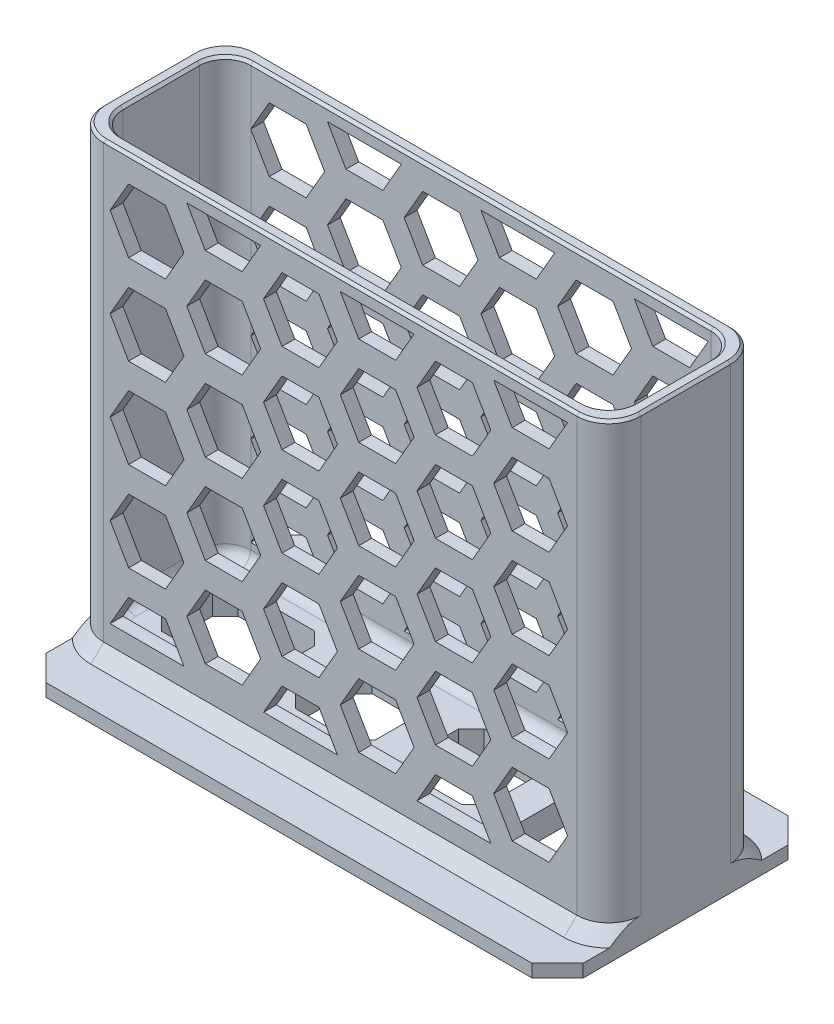
SolidWorks part; units mm, degrees
ref_plane "Front Plane" through (0, 0, 0) normal (0, 0, 1) x (1, 0, 0)
ref_plane "Top Plane" through (0, 0, 0) normal (0, 1, 0) x (1, 0, 0)
ref_plane "Right Plane" through (0, 0, 0) normal (1, 0, 0) x (0, 0, -1)
sketch "Sketch1" plane through (0, 0, 0) normal (0, 1, 0) x (1, 0, 0)
  line L1 (-105, 30) -> (105, 30)
  line L2 (-105, 30) -> (-105, -30)
  line L3 (-105, -30) -> (105, -30)
  line L4 (105, 30) -> (105, -30)
  point P0 (0, 0)
  point P6 (0, 0)
  dimension "D1" = 210
  dimension "D2" = 60
extrude "Boss-Extrude1" add sketch "Sketch1" along normal blind 5
sketch "Sketch2" plane through (0, 5, 0) normal (0, 1, 0) x (1, 0, 0)
  line L1 (-100, 25) -> (100, 25)
  line L2 (-100, 25) -> (-100, -25)
  line L3 (-100, -25) -> (100, -25)
  line L4 (100, 25) -> (100, -25)
  line L5 (-100, 25) -> (100, -25) construction
  line L6 (-100, -25) -> (100, 25) construction
  line L7 (-105, -30) -> (105, -30)
  line L8 (-105, -30) -> (-105, 30)
  line L9 (-105, 30) -> (105, 30)
  line L10 (105, -30) -> (105, 30)
  line L11 (-105, -30) -> (105, 30) construction
  line L12 (-105, 30) -> (105, -30) construction
  point P0 (0, 0)
  point P6 (0, 0)
  dimension "D1" = 200
  dimension "D2" = 50
extrude "Boss-Extrude2" add sketch "Sketch2" along normal blind 170
fillet "Fillet1" radius 10 4 edges at (100, 90, 25) (-100, 90, 25) (100, 90, -25) (-100, 90, -25)
fillet "Fillet2" radius 12.5 4 edges at (105, 87.5, 30) (105, 87.5, -30) (-105, 87.5, 30) (-105, 87.5, -30)
fillet "Fillet3" radius 5 8 edges at (97.0711, 5, -22.0711) (100, 5, 0) (97.0711, 5, 22.0711) (0, 5, 25) (-97.0711, 5, 22.0711) (-100, 5, 0) (-97.0711, 5, -22.0711) (0, 5, -25)
sketch "Sketch3" plane through (0, 0, 30) normal (0, 0, 1) x (1, 0, 0)
  line L0 (-61.1325, 117.5) -> (-68.3494, 130)
  line L1 (-61.1325, 152.5) -> (-68.3494, 165)
  line L2 (-68.3494, 165) -> (-82.7831, 165)
  line L3 (-82.7831, 165) -> (-90, 152.5)
  line L4 (-90, 152.5) -> (-82.7831, 140)
  line L5 (-82.7831, 140) -> (-68.3494, 140)
  line L6 (-68.3494, 140) -> (-61.1325, 152.5)
  line L7 (-68.3494, 130) -> (-82.7831, 130)
  line L8 (-82.7831, 130) -> (-90, 117.5)
  line L9 (-90, 117.5) -> (-82.7831, 105)
  line L10 (-82.7831, 105) -> (-68.3494, 105)
  line L11 (-68.3494, 105) -> (-61.1325, 117.5)
  line L12 (-61.1325, 82.5) -> (-68.3494, 95)
  line L13 (-68.3494, 95) -> (-82.7831, 95)
  line L14 (-82.7831, 95) -> (-90, 82.5)
  line L15 (-90, 82.5) -> (-82.7831, 70)
  line L16 (-82.7831, 70) -> (-68.3494, 70)
  line L17 (-68.3494, 70) -> (-61.1325, 82.5)
  line L18 (-61.1325, 47.5) -> (-68.3494, 60)
  line L19 (-68.3494, 60) -> (-82.7831, 60)
  line L20 (-82.7831, 60) -> (-90, 47.5)
  line L21 (-90, 47.5) -> (-82.7831, 35)
  line L22 (-82.7831, 35) -> (-68.3494, 35)
  line L23 (-68.3494, 35) -> (-61.1325, 47.5)
  line L24 (-61.1325, 12.5) -> (-68.3494, 25)
  line L25 (-68.3494, 25) -> (-82.7831, 25)
  line L26 (-82.7831, 25) -> (-90, 12.5)
  line L31 (0, 170) -> (28.8675, 170)
  line L32 (60, 170) -> (88.8675, 170)
  line L33 (-38.3494, 157.5) -> (-31.1325, 170)
  line L34 (-52.7831, 147.5) -> (-60, 135)
  line L35 (-31.1325, 100) -> (-38.3494, 112.5)
  line L36 (-38.3494, 77.5) -> (-52.7831, 77.5)
  line L37 (-38.3494, 17.5) -> (-31.1325, 30)
  line L39 (-52.7831, 52.5) -> (-38.3494, 52.5)
  line L40 (-38.3494, 147.5) -> (-52.7831, 147.5)
  line L41 (-38.3494, 52.5) -> (-31.1325, 65)
  line L42 (-31.1325, 135) -> (-38.3494, 147.5)
  line L43 (-52.7831, 157.5) -> (-38.3494, 157.5)
  line L44 (-60, 170) -> (-52.7831, 157.5)
  line L45 (-60, 135) -> (-52.7831, 122.5)
  line L46 (-31.1325, 65) -> (-38.3494, 77.5)
  line L47 (-38.3494, 122.5) -> (-31.1325, 135)
  line L48 (-52.7831, 17.5) -> (-38.3494, 17.5)
  line L49 (-52.7831, 87.5) -> (-38.3494, 87.5)
  line L50 (-38.3494, 87.5) -> (-31.1325, 100)
  line L51 (-52.7831, 42.5) -> (-60, 30)
  line L52 (-60, 100) -> (-52.7831, 87.5)
  line L53 (-31.1325, 30) -> (-38.3494, 42.5)
  line L54 (-52.7831, 77.5) -> (-60, 65)
  line L55 (-60, 65) -> (-52.7831, 52.5)
  line L57 (-38.3494, 112.5) -> (-52.7831, 112.5)
  line L58 (-52.7831, 112.5) -> (-60, 100)
  line L59 (-38.3494, 42.5) -> (-52.7831, 42.5)
  line L60 (-52.7831, 122.5) -> (-38.3494, 122.5)
  line L61 (-60, 30) -> (-52.7831, 17.5)
  line L62 (-1.1325, 117.5) -> (-8.3494, 130)
  line L63 (-1.1325, 152.5) -> (-8.3494, 165)
  line L64 (-8.3494, 165) -> (-22.7831, 165)
  line L65 (-22.7831, 165) -> (-30, 152.5)
  line L66 (-30, 152.5) -> (-22.7831, 140)
  line L67 (-22.7831, 140) -> (-8.3494, 140)
  line L68 (-8.3494, 140) -> (-1.1325, 152.5)
  line L69 (-8.3494, 130) -> (-22.7831, 130)
  line L70 (-22.7831, 130) -> (-30, 117.5)
  line L71 (-30, 117.5) -> (-22.7831, 105)
  line L72 (-22.7831, 105) -> (-8.3494, 105)
  line L73 (-8.3494, 105) -> (-1.1325, 117.5)
  line L74 (-1.1325, 82.5) -> (-8.3494, 95)
  line L75 (-8.3494, 95) -> (-22.7831, 95)
  line L76 (-22.7831, 95) -> (-30, 82.5)
  line L77 (-30, 82.5) -> (-22.7831, 70)
  line L78 (-22.7831, 70) -> (-8.3494, 70)
  line L79 (-8.3494, 70) -> (-1.1325, 82.5)
  line L80 (-1.1325, 47.5) -> (-8.3494, 60)
  line L81 (-8.3494, 60) -> (-22.7831, 60)
  line L82 (-22.7831, 60) -> (-30, 47.5)
  line L83 (-30, 47.5) -> (-22.7831, 35)
  line L84 (-22.7831, 35) -> (-8.3494, 35)
  line L85 (-8.3494, 35) -> (-1.1325, 47.5)
  line L86 (-1.1325, 12.5) -> (-8.3494, 25)
  line L87 (-8.3494, 25) -> (-22.7831, 25)
  line L88 (-22.7831, 25) -> (-30, 12.5)
  line L93 (21.6506, 157.5) -> (28.8675, 170)
  line L94 (7.2169, 147.5) -> (0, 135)
  line L95 (28.8675, 100) -> (21.6506, 112.5)
  line L96 (21.6506, 77.5) -> (7.2169, 77.5)
  line L97 (21.6506, 17.5) -> (28.8675, 30)
  line L99 (7.2169, 52.5) -> (21.6506, 52.5)
  line L100 (21.6506, 147.5) -> (7.2169, 147.5)
  line L101 (21.6506, 52.5) -> (28.8675, 65)
  line L102 (28.8675, 135) -> (21.6506, 147.5)
  line L103 (7.2169, 157.5) -> (21.6506, 157.5)
  line L104 (0, 170) -> (7.2169, 157.5)
  line L105 (0, 135) -> (7.2169, 122.5)
  line L106 (28.8675, 65) -> (21.6506, 77.5)
  line L107 (21.6506, 122.5) -> (28.8675, 135)
  line L108 (7.2169, 17.5) -> (21.6506, 17.5)
  line L109 (7.2169, 87.5) -> (21.6506, 87.5)
  line L110 (21.6506, 87.5) -> (28.8675, 100)
  line L111 (7.2169, 42.5) -> (0, 30)
  line L112 (0, 100) -> (7.2169, 87.5)
  line L113 (28.8675, 30) -> (21.6506, 42.5)
  line L114 (7.2169, 77.5) -> (0, 65)
  line L115 (0, 65) -> (7.2169, 52.5)
  line L117 (21.6506, 112.5) -> (7.2169, 112.5)
  line L118 (7.2169, 112.5) -> (0, 100)
  line L119 (21.6506, 42.5) -> (7.2169, 42.5)
  line L120 (7.2169, 122.5) -> (21.6506, 122.5)
  line L121 (0, 30) -> (7.2169, 17.5)
  line L122 (58.8675, 117.5) -> (51.6506, 130)
  line L123 (58.8675, 152.5) -> (51.6506, 165)
  line L124 (51.6506, 165) -> (37.2169, 165)
  line L125 (37.2169, 165) -> (30, 152.5)
  line L126 (30, 152.5) -> (37.2169, 140)
  line L127 (37.2169, 140) -> (51.6506, 140)
  line L128 (51.6506, 140) -> (58.8675, 152.5)
  line L129 (51.6506, 130) -> (37.2169, 130)
  line L130 (37.2169, 130) -> (30, 117.5)
  line L131 (30, 117.5) -> (37.2169, 105)
  line L132 (37.2169, 105) -> (51.6506, 105)
  line L133 (51.6506, 105) -> (58.8675, 117.5)
  line L134 (58.8675, 82.5) -> (51.6506, 95)
  line L135 (51.6506, 95) -> (37.2169, 95)
  line L136 (37.2169, 95) -> (30, 82.5)
  line L137 (30, 82.5) -> (37.2169, 70)
  line L138 (37.2169, 70) -> (51.6506, 70)
  line L139 (51.6506, 70) -> (58.8675, 82.5)
  line L140 (58.8675, 47.5) -> (51.6506, 60)
  line L141 (51.6506, 60) -> (37.2169, 60)
  line L142 (37.2169, 60) -> (30, 47.5)
  line L143 (30, 47.5) -> (37.2169, 35)
  line L144 (37.2169, 35) -> (51.6506, 35)
  line L145 (51.6506, 35) -> (58.8675, 47.5)
  line L146 (58.8675, 12.5) -> (51.6506, 25)
  line L147 (51.6506, 25) -> (37.2169, 25)
  line L148 (37.2169, 25) -> (30, 12.5)
  line L153 (81.6506, 157.5) -> (88.8675, 170)
  line L154 (67.2169, 147.5) -> (60, 135)
  line L155 (88.8675, 100) -> (81.6506, 112.5)
  line L156 (81.6506, 77.5) -> (67.2169, 77.5)
  line L157 (81.6506, 17.5) -> (88.8675, 30)
  line L159 (67.2169, 52.5) -> (81.6506, 52.5)
  line L160 (81.6506, 147.5) -> (67.2169, 147.5)
  line L161 (81.6506, 52.5) -> (88.8675, 65)
  line L162 (88.8675, 135) -> (81.6506, 147.5)
  line L163 (67.2169, 157.5) -> (81.6506, 157.5)
  line L164 (60, 170) -> (67.2169, 157.5)
  line L165 (60, 135) -> (67.2169, 122.5)
  line L166 (88.8675, 65) -> (81.6506, 77.5)
  line L167 (81.6506, 122.5) -> (88.8675, 135)
  line L168 (67.2169, 17.5) -> (81.6506, 17.5)
  line L169 (67.2169, 87.5) -> (81.6506, 87.5)
  line L170 (81.6506, 87.5) -> (88.8675, 100)
  line L171 (67.2169, 42.5) -> (60, 30)
  line L172 (60, 100) -> (67.2169, 87.5)
  line L173 (88.8675, 30) -> (81.6506, 42.5)
  line L174 (67.2169, 77.5) -> (60, 65)
  line L175 (60, 65) -> (67.2169, 52.5)
  line L177 (81.6506, 112.5) -> (67.2169, 112.5)
  line L178 (67.2169, 112.5) -> (60, 100)
  line L179 (81.6506, 42.5) -> (67.2169, 42.5)
  line L180 (67.2169, 122.5) -> (81.6506, 122.5)
  line L181 (60, 30) -> (67.2169, 17.5)
  line L182 (-60, 170) -> (-31.1325, 170)
  line L183 (-90, 12.5) -> (-61.1325, 12.5)
  line L185 (30, 12.5) -> (58.8675, 12.5)
  line L186 (-30, 12.5) -> (-1.1325, 12.5)
  line L195 (-68.3494, 0) -> (-61.1325, 12.5) [skipped]
  line L196 (-90, 12.5) -> (-82.7831, 0) [skipped]
  line L197 (-82.7831, 0) -> (-68.3494, 0) [skipped]
  dimension "D2" = 5
extrude "Cut-Extrude1" cut sketch "Sketch3" against normal blind 170
sketch "Sketch4" plane through (0, 0, 0) normal (0, -1, 0) x (1, 0, 0)
  line L1 (-105, -50) -> (105, -50)
  line L2 (-105, -50) -> (-105, 50)
  line L3 (-105, 50) -> (105, 50)
  line L4 (105, -50) -> (105, 50)
  line L5 (-105, -50) -> (105, 50) construction
  line L6 (-105, 50) -> (105, -50) construction
  point P1 (0, 0)
  dimension "D1" = 210
  dimension "D2" = 100
extrude "Boss-Extrude3" add sketch "Sketch4" along normal blind 5
chamfer "Chamfer1" distance 5 angle 45 6 edges at (101.3388, 0, -26.3388) (-101.3388, 0, -26.3388) (0, 0, -30) (-101.3388, 0, 26.3388) (101.3388, 0, 26.3388) (0, 0, 30)
chamfer "Chamfer2" distance 10 angle 45 4 edges at (-105, -2.5, -50) (105, -2.5, -50) (105, -2.5, 50) (-105, -2.5, 50)
chamfer "Chamfer3" distance 1 angle 45 16 edges at (97.0711, 175, -22.0711) (0, 175, -25) (-97.0711, 175, -22.0711) (-100, 175, 0) (-97.0711, 175, 22.0711) (0, 175, 25) (97.0711, 175, 22.0711) (100, 175, 0) (-101.3388, 175, 26.3388) (-105, 175, 0) (-101.3388, 175, -26.3388) (0, 175, -30) (101.3388, 175, -26.3388) (105, 175, 0) (101.3388, 175, 26.3388) (0, 175, 30)
sketch "Sketch5" plane through (0, 5, 0) normal (0, 1, 0) x (1, 0, 0)
  line L0 (-90, 15) -> (-50, 15)
  line L2 (-90, -15) -> (-90, 15)
  line L4 (90, -15) -> (90, 15)
  line L13 (90, -15) -> (50, -15)
  line L14 (6.25, 1.2406) -> (6.25, 15)
  line L15 (37.5, -15) -> (6.25, -15)
  line L18 (-50, 15) -> (-50, -15)
  line L20 (-37.5, 15) -> (-37.5, -15)
  line L22 (50, 0) -> (50, -15)
  line L24 (37.5, 0) -> (37.5, -15)
  line L26 (37.5, 0) -> (37.5, 15)
  line L28 (50, 0) -> (50, 15)
  line L29 (-37.5, 15) -> (-6.25, 15)
  line L35 (-6.25, 15) -> (-6.25, -15)
  line L37 (6.25, 1.2406) -> (6.25, -15)
  line L38 (-50, -15) -> (-90, -15)
  line L39 (-6.25, -15) -> (-37.5, -15)
  line L41 (6.25, 15) -> (37.5, 15)
  line L43 (50, 15) -> (90, 15)
  point P0 (0, 0)
  point P6 (0, 0)
  point P10 (0, 0)
  point P11 (0, 0)
  point P14 (0, 0)
  point P25 (0, 0)
  dimension "D1" = 180
  dimension "D2" = 30
extrude "Cut-Extrude2" cut sketch "Sketch5" against normal up to surface (10 mm away) up to face at (0, -5, 0)
chamfer "Chamfer4" distance 5 angle 45 16 edges at (6.25, 0, 15) (50, 0, 15) (90, 0, -15) (37.5, 0, -15) (90, 0, 15) (37.5, 0, 15) (-6.25, 0, 15) (6.25, 0, -15) (50, 0, -15) (-37.5, 0, -15) (-50, 0, 15) (-37.5, 0, 15) (-90, 0, 15) (-50, 0, -15) (-90, 0, -15) (-6.25, 0, -15)
